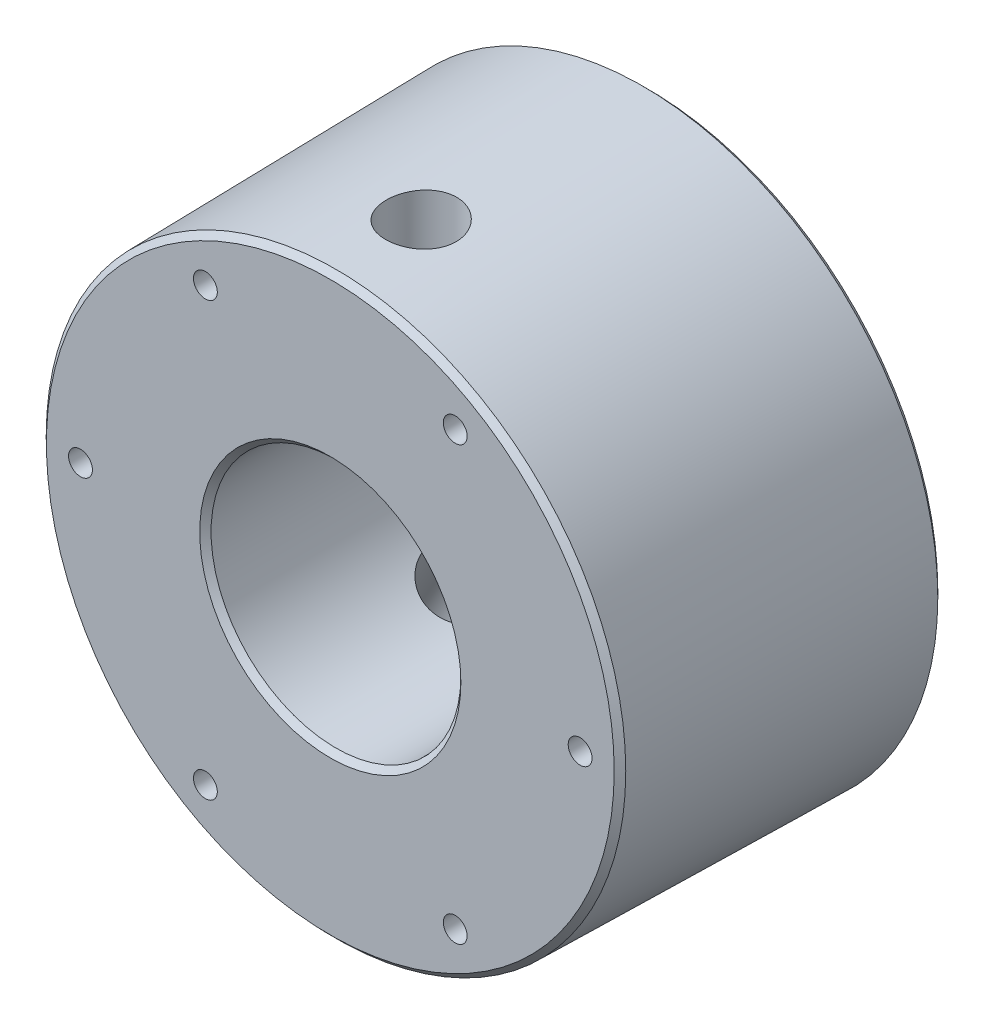
SolidWorks part; units mm, degrees
ref_plane "前视基准面" through (0, 0, 0) normal (0, 0, 1) x (1, 0, 0)
ref_plane "上视基准面" through (0, 0, 0) normal (0, 1, 0) x (1, 0, 0)
ref_plane "右视基准面" through (0, 0, 0) normal (1, 0, 0) x (0, 0, -1)
other "Configuration Table"
sketch "Sk_body" plane through (0, 0, 0) normal (0, 0, 1) x (1, 0, 0)
  circle A0 centre (0, 0) radius 52
extrude "Body_draft1" add sketch "Sk_body" along normal blind 56 draft 1
ref_plane "P10" through (0, 0, 10) normal (0, 0, 1) x (1, 0, 0)
sketch "Sk_b20" plane through (0, 0, 0) normal (0, 0, 1) x (1, 0, 0)
  circle A0 centre (0, 0) radius 10
extrude "Cut_b20" cut sketch "Sk_b20" along normal blind 10
ref_plane "P22" through (0, 0, 22) normal (0, 0, 1) x (1, 0, 0)
sketch "Sk_pl0" plane through (0, 0, 22) normal (0, 0, 1) x (1, 0, 0)
  line L0 (21, 0) -> (48, 0)
  line L1 (48, 0) -> (48, 6.25)
  line L2 (48, 6.25) -> (21, 6.25)
  line L3 (21, 6.25) -> (21, 0)
  line L4 (0, 0) -> (50, 0) construction
revolve "Cut_pl0" cut sketch "Sk_pl0" angle 360 about L4
sketch "Sk_cav2" plane through (0, 0, 10) normal (0, 0, 1) x (1, 0, 0)
  circle A0 centre (0, 0) radius 22
extrude "Cut_cav44b" cut sketch "Sk_cav2" along normal blind 46
ref_plane "P21" through (0, 0, 21) normal (0, 0, 1) x (1, 0, 0)
sketch "Sk_notch120" plane through (0, 0, 21) normal (0, 0, 1) x (1, 0, 0)
  line L0 (-24.466, 40.3764) -> (-22.734, 41.3764)
  line L1 (-22.734, 41.3764) -> (-23.134, 42.0692)
  line L2 (-23.134, 42.0692) -> (-24.866, 41.0692)
  line L3 (-24.866, 41.0692) -> (-24.466, 40.3764)
extrude "Cut_notch120" cut sketch "Sk_notch120" along normal blind 2
sketch "Sk_h120" plane through (-24.0005, 41.5689, 0) normal (0.5, -0.866, 0) x (0.866, 0.5, 0)
  circle A0 centre (0.0006, 22) radius 6.25
extrude "Cut_pl120c" cut sketch "Sk_h120" along normal blind 26.9
sketch "Sk_notch240" plane through (0, 0, 21) normal (0, 0, 1) x (1, 0, 0)
  line L0 (-22.734, -41.3764) -> (-24.466, -40.3764)
  line L1 (-24.466, -40.3764) -> (-24.866, -41.0692)
  line L2 (-24.866, -41.0692) -> (-23.134, -42.0692)
  line L3 (-23.134, -42.0692) -> (-22.734, -41.3764)
extrude "Cut_notch240" cut sketch "Sk_notch240" along normal blind 2
sketch "Sk_h240" plane through (-24.0005, -41.5689, 0) normal (0.5, 0.866, 0) x (0.866, -0.5, 0)
  circle A0 centre (0.0006, -22) radius 6.25
extrude "Cut_pl240c" cut sketch "Sk_h240" along normal blind 26.9
sketch "Sk_p5" plane through (0, 0, 0) normal (0, 0, 1) x (1, 0, 0)
  circle A0 centre (26, 0) radius 2.5
  circle A1 centre (-13, 22.5167) radius 2.5
  circle A2 centre (-13, -22.5167) radius 2.5
extrude "Cut_p5x3" cut sketch "Sk_p5" along normal blind 22
ref_plane "P44" through (0, 0, 44) normal (0, 0, 1) x (1, 0, 0)
ref_plane "P39" through (0, 0, 39) normal (0, 0, 1) x (1, 0, 0)
chamfer "Chamfer_C1" distance 1 angle 45 5 edges at (22, 0, 56) (10, 0, 0) (10, 0, 10) (52, 0, 0) (51.0225, 0, 56) first distance on face at (22, 0, 56) first distance on face at (10, 0, 10) first distance on face at (28.5, 0, 0) first distance on face at (51.0225, 0, 56)
ref_plane "P40" through (0, 0, 40) normal (0, 0, 1) x (1, 0, 0)
sketch "Sk_m5v12" plane through (0, 0, 40) normal (0, 0, 1) x (1, 0, 0)
  circle A0 centre (44, 0) radius 2.1
  circle A1 centre (22, 38.1051) radius 2.1
  circle A2 centre (-22, 38.1051) radius 2.1
  circle A3 centre (-44, 0) radius 2.1
  circle A4 centre (-22, -38.1051) radius 2.1
  circle A5 centre (22, -38.1051) radius 2.1
extrude "Cut_m5v12" cut sketch "Sk_m5v12" along normal blind 16
sketch "Sk_notch90" plane through (0, 0, 39) normal (0, 0, 1) x (1, 0, 0)
  line L0 (-1, 30) -> (1, 30)
  line L1 (1, 30) -> (1, 30.8)
  line L2 (1, 30.8) -> (-1, 30.8)
  line L3 (-1, 30.8) -> (-1, 30)
extrude "Cut_notch90" cut sketch "Sk_notch90" along normal blind 2
sketch "Sk_oil90" plane through (0, 30, 0) normal (0, 1, 0) x (1, 0, 0)
  circle A0 centre (0, -40) radius 6.25
extrude "Cut_oil90" cut sketch "Sk_oil90" along normal blind 22
sketch "Sk_notch270" plane through (0, 0, 39) normal (0, 0, 1) x (1, 0, 0)
  line L0 (1, -30) -> (-1, -30)
  line L1 (-1, -30) -> (-1, -30.8)
  line L2 (-1, -30.8) -> (1, -30.8)
  line L3 (1, -30.8) -> (1, -30)
extrude "Cut_notch270" cut sketch "Sk_notch270" along normal blind 2
sketch "Sk_oil270" plane through (0, -30, 0) normal (0, -1, 0) x (1, 0, 0)
  circle A0 centre (0, 40) radius 6.25
extrude "Cut_oil270" cut sketch "Sk_oil270" along normal blind 22
